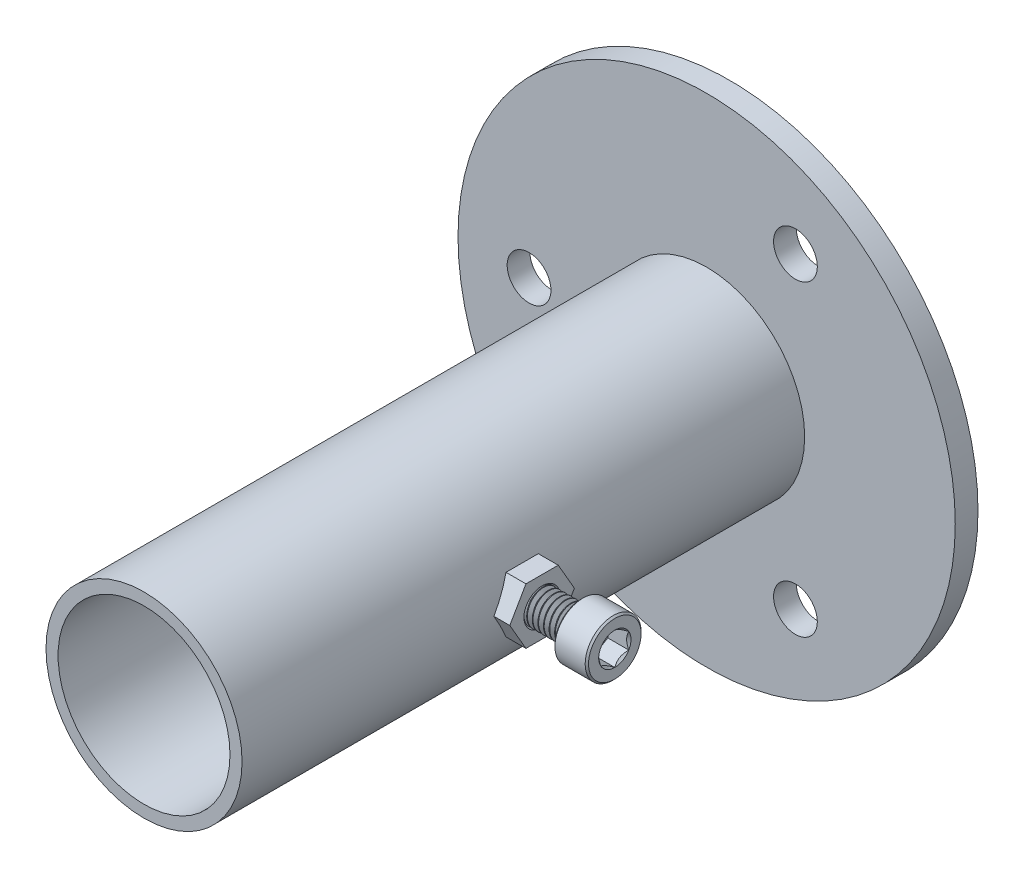
SolidWorks part; units mm, degrees
ref_plane "Front Plane" through (0, 0, 0) normal (0, 0, 1) x (1, 0, 0)
ref_plane "Top Plane" through (0, 0, 0) normal (0, 1, 0) x (1, 0, 0)
ref_plane "Right Plane" through (0, 0, 0) normal (1, 0, 0) x (0, 0, -1)
sketch "Sketch1" plane through (0, 0, 0) normal (0, 0, 1) x (1, 0, 0)
  line L0 (15.875, 27.4963) -> (-31.75, 0) construction
  line L5 (-31.75, 0) -> (15.875, -27.4963) construction
  line L6 (15.875, -27.4963) -> (15.875, 27.4963) construction
  circle A0 centre (0, 0) radius 44.45 construction
  circle A1 centre (0, 0) radius 31.75 construction
  circle A2 centre (-31.75, 0) radius 3.9116 construction
  circle A3 centre (15.875, 27.4963) radius 3.9116 construction
  circle A4 centre (15.875, -27.4963) radius 3.9116 construction
  circle A5 centre (0, 0) radius 9.5885 construction
  circle A6 centre (0, 0) radius 15.367
  circle A7 centre (0, 0) radius 17.526
  point P13 (15.367, 0)
  dimension "D1" = 88.9
  dimension "D2" = 63.5
  dimension "D3" = 35.052
  dimension "D4" = 30.734
  dimension "D5" = 7.8232
  dimension "D6" = 19.177
  dimension "D7" = 54.9926
sketch "Sketch2" plane through (0, 0, 0) normal (1, 0, 0) x (0, 0, -1)
  line L0 (-104.648, 0) -> (0, 0) construction
  point P3 (-4.064, 0)
  point P5 (-53.848, 0)
  dimension "D1" = 100.584
  dimension "D2" = 4.064
  dimension "D3" = 50.8
sketch "Sketch3" plane through (0, 0, 0) normal (0, 0, 1) x (1, 0, 0)
  circle A0 centre (0, 0) radius 44.45 construction
  circle A1 centre (0, 0) radius 44.45
  circle A2 centre (0, 0) radius 9.5885 construction
  circle A3 centre (0, 0) radius 9.5885
extrude "Boss-Extrude1" add sketch "Sketch3" along normal up to vertex (4.064 mm away) up to point (0, 0, 4.064)
sketch "Sketch4" plane through (0, 0, 4.064) normal (0, 0, 1) x (1, 0, 0)
  circle A0 centre (-31.75, 0) radius 3.9116 construction
  circle A1 centre (15.875, 27.4963) radius 3.9116 construction
  circle A2 centre (15.875, -27.4963) radius 3.9116 construction
  circle A3 centre (-31.75, 0) radius 3.9116
  circle A4 centre (15.875, 27.4963) radius 3.9116
  circle A5 centre (15.875, -27.4963) radius 3.9116
extrude "Cut-Extrude2" cut sketch "Sketch4" against normal up to next
sketch "Sketch5" plane through (0, 0, 4.064) normal (0, 0, 1) x (1, 0, 0)
  circle A0 centre (0, 0) radius 15.367 construction
  circle A1 centre (0, 0) radius 17.526 construction
  circle A2 centre (0, 0) radius 15.367
  circle A3 centre (0, 0) radius 17.526
extrude "Boss-Extrude2" add sketch "Sketch5" along normal up to vertex (100.584 mm away) up to point (0, 0, 104.648)
sketch "Sketch6" plane through (0, 0, 0) normal (1, 0, 0) x (0, 0, -1)
  line L0 (-104.648, 0) -> (0, 0) construction
  line L1 (-59.6215, 0) -> (-56.7348, -5)
  line L2 (-56.7348, -5) -> (-50.9612, -5)
  line L3 (-50.9612, -5) -> (-48.0745, 0)
  line L4 (-48.0745, 0) -> (-50.9612, 5)
  line L5 (-50.9612, 5) -> (-56.7348, 5)
  line L6 (-56.7348, 5) -> (-59.6215, 0)
  circle A0 centre (-53.848, 0) radius 5 construction
  dimension "D1" = 10
extrude "Cut-Extrude3" cut sketch "Sketch6" along normal up to next
ref_plane "Plane1" through (15.367, 0, 0) normal (1, 0, 0) x (0, 0, -1)
sketch "Sketch7" plane through (15.367, 0, 0) normal (1, 0, 0) x (0, 0, -1)
  line L6 (-59.6215, 0) -> (-56.7348, -5)
  line L7 (-56.7348, -5) -> (-50.9612, -5)
  line L8 (-50.9612, -5) -> (-48.0745, 0)
  line L9 (-48.0745, 0) -> (-50.9612, 5)
  line L10 (-50.9612, 5) -> (-56.7348, 5)
  line L11 (-56.7348, 5) -> (-59.6215, 0)
  line L12 (-59.6215, 0) -> (-56.7348, -5)
  line L13 (-56.7348, -5) -> (-50.9612, -5)
  line L14 (-50.9612, -5) -> (-48.0745, 0)
  line L15 (-48.0745, 0) -> (-50.9612, 5)
  line L16 (-50.9612, 5) -> (-56.7348, 5)
  line L17 (-56.7348, 5) -> (-59.6215, 0)
  circle A0 centre (-53.848, 0) radius 3
  dimension "D2" = 6
  dimension "D1" = 0
extrude "Boss-Extrude3" add sketch "Sketch7" along normal blind 5
chamfer "Chamfer1" distance 0.25 angle 45 2 edges at (15.367, 0, 50.848) (20.367, 0, 50.848)
sketch "Sketch8" plane through (15.367, 0, 0) normal (1, 0, 0) x (0, 0, -1)
  circle A1 centre (-53.848, 0) radius 3
  circle A2 centre (-53.848, 0) radius 3
  dimension "D1" = 0
extrude "Boss-Extrude4" add sketch "Sketch8" along normal blind 12 separate body
sketch "Sketch9" plane through (15.367, 0, 0) normal (-1, 0, 0) x (0, 0, 1)
  circle A1 centre (53.848, 0) radius 3
  circle A2 centre (53.848, 0) radius 3
  point P0 (53.848, 3)
  dimension "D1" = 0
curve "Helix/Spiral1" pitch 1 height 13 turns 13
ref_plane "Plane2" through (0, 0, 53.848) normal (0, 0, 1) x (1, 0, 0)
sketch "Sketch10" plane through (0, 0, 53.848) normal (0, 0, 1) x (1, 0, 0)
  line L0 (14.4295, 3.1083) -> (14.9295, 2.2422) construction
  line L1 (14.9295, 2.2422) -> (15.4295, 3.1083) construction
  line L2 (15.4295, 3.1083) -> (14.4295, 3.1083) construction
  line L3 (14.867, 2.3505) -> (14.992, 2.3505) construction
  line L4 (14.492, 3) -> (15.367, 3) construction
  line L5 (14.9295, 2.2422) -> (14.9295, 2.3505) construction
  line L6 (14.9295, 3) -> (14.9295, 3.1083) construction
  line L7 (14.4608, 3.0541) -> (14.867, 2.3505)
  line L8 (14.867, 2.3505) -> (14.992, 2.3505)
  line L9 (14.992, 2.3505) -> (15.3983, 3.0541)
  line L10 (15.3983, 3.0541) -> (14.4608, 3.0541)
  point P15 (14.9295, 3.0541)
  dimension "D1" = 1
  dimension "D2" = 0.125
sweep "Cut-Sweep1" cut profiles "Sketch10" path "Helix/Spiral1"
sketch "Sketch11" plane through (15.367, 0, 0) normal (-1, 0, 0) x (0, 0, 1)
  circle A0 centre (53.848, 0) radius 2.2422
extrude "Cut-Extrude4" cut sketch "Sketch11" against normal through all draft 45 flip side to cut
sketch "Sketch12" plane through (27.367, 0, 0) normal (1, 0, 0) x (0, 0, -1)
  circle A0 centre (-53.848, 0) radius 5
  dimension "D1" = 10
extrude "Boss-Extrude5" add sketch "Sketch12" along normal blind 6
chamfer "Chamfer2" distance 0.3 angle 45 2 edges at (27.367, 0, 48.848) (33.367, 0, 48.848)
sketch "Sketch13" plane through (33.367, 0, 0) normal (1, 0, 0) x (0, 0, -1)
  line L1 (-53.848, 2.8868) -> (-56.348, 1.4434)
  line L2 (-56.348, 1.4434) -> (-56.348, -1.4434)
  line L3 (-56.348, -1.4434) -> (-53.848, -2.8868)
  line L4 (-53.848, -2.8868) -> (-51.348, -1.4434)
  line L5 (-51.348, -1.4434) -> (-51.348, 1.4434)
  line L6 (-51.348, 1.4434) -> (-53.848, 2.8868)
  circle A0 centre (-53.848, 0) radius 2.5 construction
  dimension "D1" = 5
extrude "Cut-Extrude5" cut sketch "Sketch13" against normal blind 3.75
sketch "Sketch14" plane through (33.367, 0, 0) normal (1, 0, 0) x (0, 0, -1)
  circle A0 centre (-53.848, 0) radius 2.8868
extrude "Cut-Extrude6" cut sketch "Sketch14" against normal up to next (3.75 mm away) draft 45
equation "\"D3@Helix/Spiral1\" = \"D4@Helix/Spiral1\" + \"D1@Boss-Extrude4\""
equation "\"D1@Sketch10\" = \"D4@Helix/Spiral1\""
equation "\"D2@Sketch10\" = \"D1@Sketch10\" / 8"
